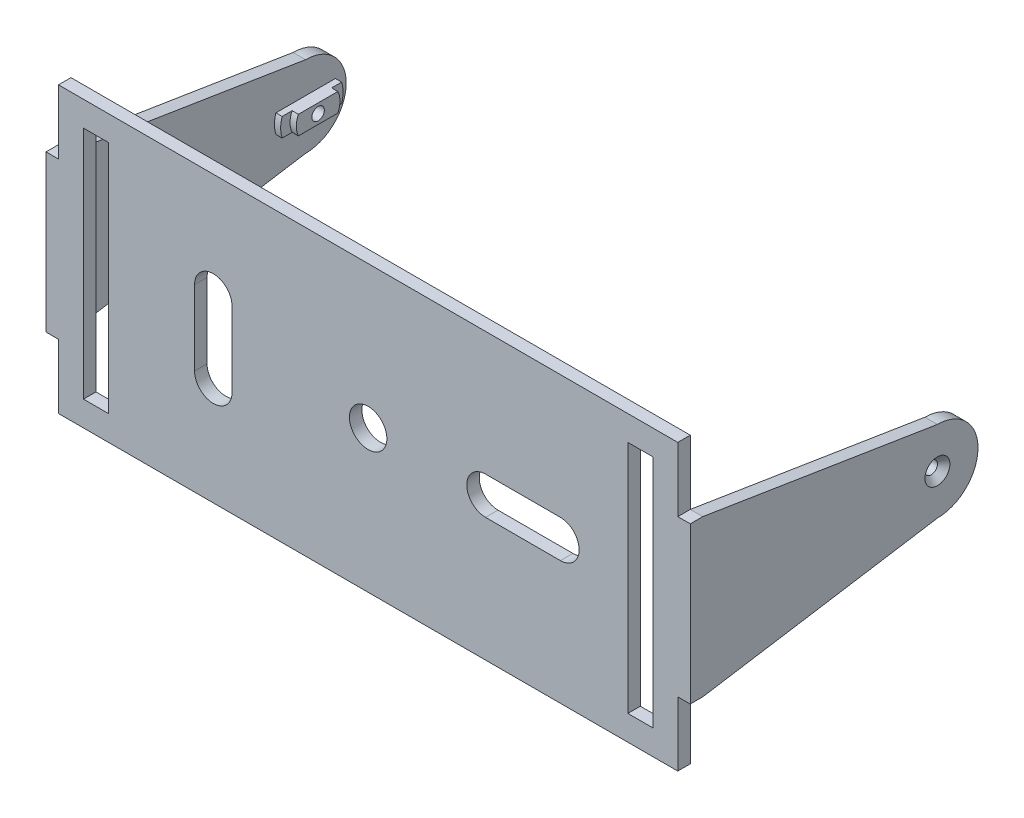
SolidWorks part; units mm, degrees
ref_plane "Спереди" through (0, 0, 0) normal (0, 0, 1) x (1, 0, 0)
ref_plane "Сверху" through (0, 0, 0) normal (0, 1, 0) x (1, 0, 0)
ref_plane "Справа" through (0, 0, 0) normal (1, 0, 0) x (0, 0, -1)
ref_plane "Плоскость1" through (0, 0, 5) normal (0, 0, 1) x (1, 0, 0)
sketch "Эскиз2" plane through (0, 0, 5) normal (0, 0, 1) x (1, 0, 0)
  line L0 (46.4, -1.2) -> (46.4, 21.6) construction
  line L1 (47.4, -1.2) -> (-2.2, -1.2)
  line L2 (47.4, -1.2) -> (47.4, 21.6)
  line L3 (47.4, 21.6) -> (-2.2, 21.6)
  line L4 (-2.2, -1.2) -> (-2.2, 21.6)
  line L5 (-1.2, -1.2) -> (46.4, -1.2) construction
  line L6 (46.4, 21.6) -> (-1.2, 21.6) construction
  line L7 (-1.2, 21.6) -> (-1.2, -1.2) construction
  dimension "D1" = 1
  dimension "D2" = 1
extrude "Бобышка-Вытянуть1" add sketch "Эскиз2" along normal blind 1
sketch "Эскиз3" plane through (-2.2, 0, 0) normal (-1, 0, 0) x (0, 0, 1)
  line L0 (6, 10.2) -> (-24.0506, 10.2) construction
  line L1 (6, 21.6) -> (6, -1.2) construction
  line L3 (-13.7945, 6.95) -> (6, 6.95)
  line L4 (-13.7945, 6.95) -> (-13.7945, 13.45)
  line L5 (-13.7945, 13.45) -> (6, 13.45)
  line L6 (6, 6.95) -> (6, 13.45)
  line L7 (-13.7945, 6.95) -> (6, 13.45) construction
  line L8 (-13.7945, 13.45) -> (6, 6.95) construction
  circle A0 centre (-13.7945, 10.2) radius 3.25
  arc A1 (-14.5445, 13.3623) -> (-14.5445, 7.0377) centre (-13.7945, 10.2) ccw construction
  point P4 (-3.8973, 10.2)
extrude "Бобышка-Вытянуть2" add sketch "Эскиз3" along normal blind 1 contours L4 A0 | L5 L6 L3 L4 region at (-2.2, 10.2, -15.1739)
sketch "Эскиз4" plane through (-3.2, 0, 0) normal (-1, 0, 0) x (0, 0, 1)
  circle A0 centre (-13.7945, 10.2) radius 0.5
  dimension "D1" = 1
extrude "Вырез-Вытянуть1" cut sketch "Эскиз4" against normal up to surface (1 mm away) up to face at (-2.2, 10.2, -5.2098)
sketch "Эскиз5" plane through (-2.2, 0, 0) normal (1, 0, 0) x (0, 0, -1)
  circle A0 centre (13.7945, 10.2) radius 2.5
  circle A1 centre (13.7945, 10.2) radius 0.5
  dimension "D1" = 5
  dimension "D2" = 1
extrude "Бобышка-Вытянуть3" add sketch "Эскиз5" along normal blind 0.5
sketch "Эскиз6" plane through (-1.7, 0, 0) normal (1, 0, 0) x (0, 0, -1)
  circle A0 centre (13.7945, 10.2) radius 0.5
  circle A1 centre (13.7945, 10.2) radius 1.75
  dimension "D1" = 1
  dimension "D2" = 3.5
extrude "Бобышка-Вытянуть4" add sketch "Эскиз6" along normal blind 0.5
sketch "Эскиз7" plane through (-1.2, 0, 0) normal (1, 0, 0) x (0, 0, -1)
  line L0 (13.7945, 10.2) -> (13.7945, 10.95) construction
  line L1 (11.2945, 10.95) -> (16.2945, 10.95)
  line L2 (11.2945, 10.95) -> (11.2945, 12.7)
  line L3 (11.2945, 12.7) -> (16.2945, 12.7)
  line L4 (16.2945, 10.95) -> (16.2945, 12.7)
  line L5 (16.2945, 9.45) -> (11.2945, 9.45)
  line L6 (16.2945, 9.45) -> (16.2945, 7.7)
  line L7 (16.2945, 7.7) -> (11.2945, 7.7)
  line L8 (11.2945, 9.45) -> (11.2945, 7.7)
  line L9 (13.7945, 10.2) -> (13.7945, 9.45) construction
  arc A0 (14.5445, 7.8152) -> (14.5445, 12.5849) centre (13.7945, 10.2) ccw construction
  arc A1 (13.0445, 12.5849) -> (13.0445, 7.8152) centre (13.7945, 10.2) ccw construction
  circle A2 centre (13.7945, 10.2) radius 2.5 construction
  dimension "D1" = 1.5
extrude "Вырез-Вытянуть2" cut sketch "Эскиз7" against normal up to surface (1 mm away) up to face at (-2.2, 10.2, -5.2098)
ref_plane "Плоскость2" through (22.6, 0, 0) normal (-1, 0, 0) x (0, 0, 1)
mirror "Зеркальное отражение1" about plane through (22.6, 0, 0) normal (-1, 0, 0) of "Вырез-Вытянуть2", "Бобышка-Вытянуть4", "Бобышка-Вытянуть3", "Вырез-Вытянуть1", "Бобышка-Вытянуть2"
sketch "Эскиз9" plane through (-3.2, 0, 0) normal (-1, 0, 0) x (0, 0, 1)
  line L0 (-13.2945, 10.2) -> (6.035, 10.2) construction
  line L1 (-13.7945, 13.45) -> (6, 13.45)
  line L2 (-13.7945, 13.45) -> (6, 13.45) construction
  line L3 (6, 13.45) -> (6, 16.45)
  line L4 (6, 16.45) -> (5, 16.45)
  line L5 (5, -12.54) -> (5, 12.54) construction
  line L6 (5, 16.45) -> (-13.7945, 13.45)
  line L7 (6, 6.95) -> (6, 13.45) construction
  line L8 (5, 3.95) -> (-13.7945, 6.95)
  line L9 (6, 3.95) -> (5, 3.95)
  line L10 (6, 6.95) -> (6, 3.95)
  line L11 (-13.7945, 6.95) -> (6, 6.95)
  circle A0 centre (-13.7945, 10.2) radius 0.5 construction
  dimension "D1" = 3
extrude "Бобышка-Вытянуть6" add sketch "Эскиз9" against normal blind 1
mirror "Зеркальное отражение3" about plane through (22.6, 0, 0) normal (-1, 0, 0) of "Бобышка-Вытянуть6"
chamfer "Фаска1" distance 0.5 angle 45 2 edges at (-3.2, 9.7, -13.7945) (48.4, 9.7, -13.7945)
sketch "Эскиз10" plane through (0, 0, 5) normal (0, 0, -1) x (-1, 0, 0)
  line L0 (-47.4, 10.2) -> (2.2, 10.2) construction
  line L1 (-47.4, 3.95) -> (-47.4, 16.45) construction
  line L2 (2.2, 10.95) -> (2.2, 9.45) construction
  line L3 (-35, 21.6) -> (-35, -1.2) construction
  line L4 (-47.4, 21.6) -> (2.2, 21.6) construction
  line L5 (2.2, -1.2) -> (-47.4, -1.2) construction
  line L6 (-22.6, 21.6) -> (-22.6, -1.2) construction
  line L7 (-10.2, 21.6) -> (-10.2, -1.2) construction
  line L8 (-35, 21.6) -> (-22.6, 21.6) construction
  line L9 (-22.6, 21.6) -> (-10.2, 21.6) construction
  line L10 (-35, 21.6) -> (-47.4, 21.6) construction
  line L12 (-32, 8.7) -> (-38, 8.7)
  line L13 (-32, 8.7) -> (-32, 11.7)
  line L14 (-32, 11.7) -> (-38, 11.7)
  line L15 (-38, 8.7) -> (-38, 11.7)
  line L16 (-32, 8.7) -> (-38, 11.7) construction
  line L17 (-32, 11.7) -> (-38, 8.7) construction
  line L18 (-8.7, 7.2) -> (-11.7, 7.2)
  line L19 (-8.7, 7.2) -> (-8.7, 13.2)
  line L20 (-8.7, 13.2) -> (-11.7, 13.2)
  line L21 (-11.7, 7.2) -> (-11.7, 13.2)
  line L22 (-8.7, 7.2) -> (-11.7, 13.2) construction
  line L23 (-8.7, 13.2) -> (-11.7, 7.2) construction
  circle A0 centre (-22.6, 10.2) radius 1.5
  arc A1 (-38, 8.7) -> (-38, 11.7) centre (-38, 10.2) cw
  arc A2 (-32, 11.7) -> (-32, 8.7) centre (-32, 10.2) cw
  arc A3 (-8.7, 13.2) -> (-11.7, 13.2) centre (-10.2, 13.2) ccw
  arc A4 (-8.7, 7.2) -> (-11.7, 7.2) centre (-10.2, 7.2) cw
  point P17 (-35, 10.2)
  point P23 (-10.2, 10.2)
  dimension "D1" = 3
  dimension "D2" = 3
  dimension "D3" = 6
extrude "Вырез-Вытянуть3" cut sketch "Эскиз10" against normal up to surface (1 mm away) contours A1 L15 | A2 L13 | L15 L12 L13 L14 | A4 L18 | L21 L18 L19 L20 | L20 A3 | A0 region at (35, 10.2, 5) region at (31.3634, 10.2, 5) region at (38.6366, 10.2, 5) region at (10.2, 6.5634, 5) region at (10.2, 10.2, 5) region at (10.2, 13.8366, 5) region at (22.6, 10.2, 5) up to face at (22.6, 10.2, 6)
sketch "Эскиз11" plane through (0, 0, 6) normal (0, 0, 1) x (1, 0, 0)
  line L0 (-0.2, 19.6) -> (1.8, 19.6) construction
  line L1 (-3.2, 10.2) -> (48.4, 10.2) construction
  line L2 (-0.2, 19.6) -> (1.8, 19.6)
  line L3 (-0.2, 19.6) -> (-0.2, 0.8)
  line L4 (-0.2, 10.2) -> (1.8, 10.2)
  line L5 (1.8, 19.6) -> (1.8, 0.8)
  line L6 (-3.2, 3.95) -> (-3.2, 16.45) construction
  line L7 (48.4, 3.95) -> (48.4, 16.45) construction
  line L8 (22.6, 21.6) -> (22.6, -1.3021) construction
  line L9 (47.4, 21.6) -> (-2.2, 21.6) construction
  line L10 (43.4, 19.6) -> (43.4, 0.8)
  line L11 (45.4, 10.2) -> (43.4, 10.2)
  line L12 (45.4, 19.6) -> (45.4, 0.8)
  line L13 (45.4, 19.6) -> (43.4, 19.6)
  line L14 (-0.2, 0.8) -> (1.8, 0.8)
  line L15 (45.4, 0.8) -> (43.4, 0.8)
extrude "Вырез-Вытянуть4" cut sketch "Эскиз11" against normal up to surface (1 mm away) contours L3 L14 L5 L4 | L5 L2 L3 L4 | L15 L12 L11 L10 | L12 L13 L10 L11 region at (0.8, 14.9, 6) region at (0.8, 5.5, 6) region at (44.4, 14.9, 6) region at (44.4, 5.5, 6) up to face at (22.6, 10.2, 5)
